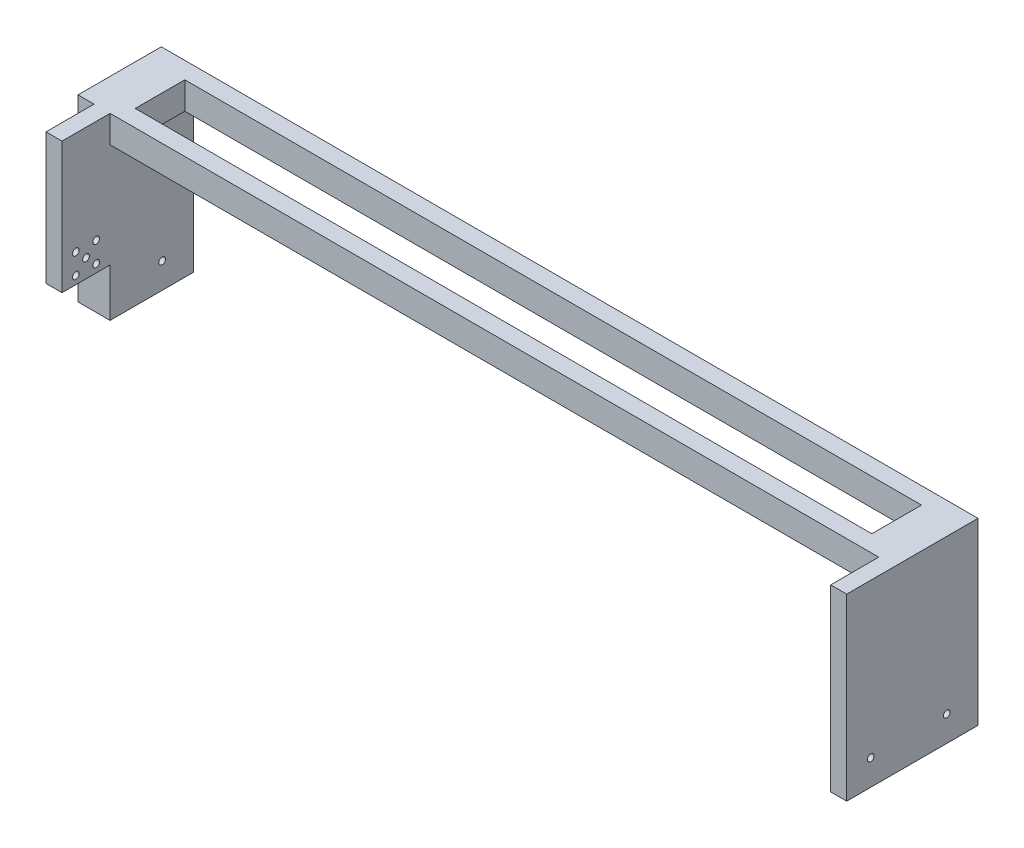
SolidWorks part; units mm, degrees
ref_plane "Front Plane" through (0, 0, 0) normal (0, 0, 1) x (1, 0, 0)
ref_plane "Top Plane" through (0, 0, 0) normal (0, 1, 0) x (1, 0, 0)
ref_plane "Right Plane" through (0, 0, 0) normal (1, 0, 0) x (0, 0, -1)
sketch "Sketch1" plane through (0, 0, 0) normal (0, 1, 0) x (1, 0, 0)
  line L0 (10, -82) -> (10, -52)
  line L1 (10, -52) -> (0, -52)
  line L2 (0, -52) -> (0, 0)
  line L4 (0, 0) -> (510, 0)
  line L5 (510, 0) -> (510, -82)
  line L8 (510, -82) -> (500, -82)
  line L9 (20, -82) -> (20, -52)
  line L10 (20, -52) -> (500, -52)
  line L11 (500, -52) -> (500, -82)
  line L12 (20, -82) -> (10, -82)
  dimension "D1" = 480
  dimension "D2" = 510
  dimension "D3" = 10
  dimension "D4" = 10
  dimension "D5" = 52
  dimension "D6" = 30
  dimension "D7" = 30
extrude "Boss-Extrude1" add sketch "Sketch1" along normal blind 82 and the other way blind 0.001 contours L9 L10 L11 L8 L5 L4 L2 L1 L0 L12
sketch "Sketch2" plane through (0, 0, 0) normal (0, 0, 1) x (1, 0, 0)
  line L0 (20, -0.001) -> (20, 64.999)
  line L1 (20, 82) -> (20, -0.001) construction
  line L2 (20, 64.999) -> (500, 64.999)
  line L3 (500, 82) -> (500, -0.001) construction
  line L4 (500, 64.999) -> (500, -0.001)
  line L5 (500, -0.001) -> (20, -0.001)
  dimension "D1" = 65
extrude "Cut-Extrude2" cut sketch "Sketch2" along normal blind 82
sketch "Sketch3" plane through (0, 0, 0) normal (0, 1, 0) x (1, 0, 0)
  line L0 (20, -82) -> (20, -52) construction
  line L1 (0, 0) -> (20, 0)
  line L2 (0, 0) -> (0, -52)
  line L3 (0, -52) -> (20, -52)
  line L4 (20, 0) -> (20, -52)
  line L5 (0, 0) -> (510, 0) construction
  line L6 (500, 0) -> (510, 0)
  line L7 (500, 0) -> (500, -82)
  line L8 (500, -82) -> (510, -82)
  line L9 (510, 0) -> (510, -82)
  line L10 (500, -52) -> (500, -82) construction
  line L11 (10, -52) -> (0, -52) construction
extrude "Boss-Extrude3" add sketch "Sketch3" against normal blind 30
sketch "Sketch4" plane through (510, 0, 0) normal (1, 0, 0) x (0, 0, -1)
  line L0 (-82, -30) -> (0, -30) construction
  line L2 (-82, -30) -> (-82, 82) construction
  circle A0 centre (-67, -14.051) radius 2.1
  circle A1 centre (-19.5, -14.05) radius 2.1
  dimension "D1" = 4.2
  dimension "D2" = 4.2
  dimension "D3" = 15.949
  dimension "D4" = 15
  dimension "D5" = 15.95
  dimension "D6" = 47.5
extrude "Cut-Extrude3" cut sketch "Sketch4" against normal blind 618
sketch "Sketch5" plane through (0, 82, 0) normal (0, 1, 0) x (1, 0, 0)
  line L0 (25.2, 0) -> (25.2, -52) construction
  line L1 (0, 0) -> (510, 0) construction
  line L3 (20, -52) -> (500, -52) construction
  line L4 (485.2, 0) -> (485.2, -52) construction
  line L5 (485.2, -514.4737) -> (485.2, 535.5263) construction
  line L6 (25.2, -10.5) -> (485.2, -10.5)
  line L7 (25.2, -10.5) -> (25.2, -41.5)
  line L8 (25.2, -41.5) -> (485.2, -41.5)
  line L9 (485.2, -41.5) -> (485.2, -10.5)
  line L10 (25.2, -514.4737) -> (25.2, 535.5263) construction
  dimension "D1" = 10.5
  dimension "D2" = 31
extrude "Cut-Extrude4" cut sketch "Sketch5" against normal blind 42
sketch "Sketch6" plane through (20, 0, 0) normal (1, 0, 0) x (0, 0, -1)
  line L0 (-82, -0.001) -> (-52, -0.001) construction
  line L3 (-67, -0.001) -> (-67, 29.5711) construction
  circle A0 centre (-67, 11.349) radius 2.1
  circle A1 centre (-60.65, 17.699) radius 2.1
  circle A2 centre (-73.35, 17.699) radius 2.1
  circle A3 centre (-73.35, 4.999) radius 2.1
  circle A4 centre (-60.65, 4.999) radius 2.1
  dimension "D5" = 4.2
  dimension "D6" = 12.7
  dimension "D1" = 12.7
  dimension "D2" = 6.35
  dimension "D3" = 12.7
  dimension "D4" = 6.35
  dimension "D7" = 6.35
  dimension "D8" = 6.35
  dimension "D9" = 6.35
  dimension "D10" = 5
  dimension "D11" = 29.5721
extrude "Cut-Extrude5" cut sketch "Sketch6" against normal blind 10
